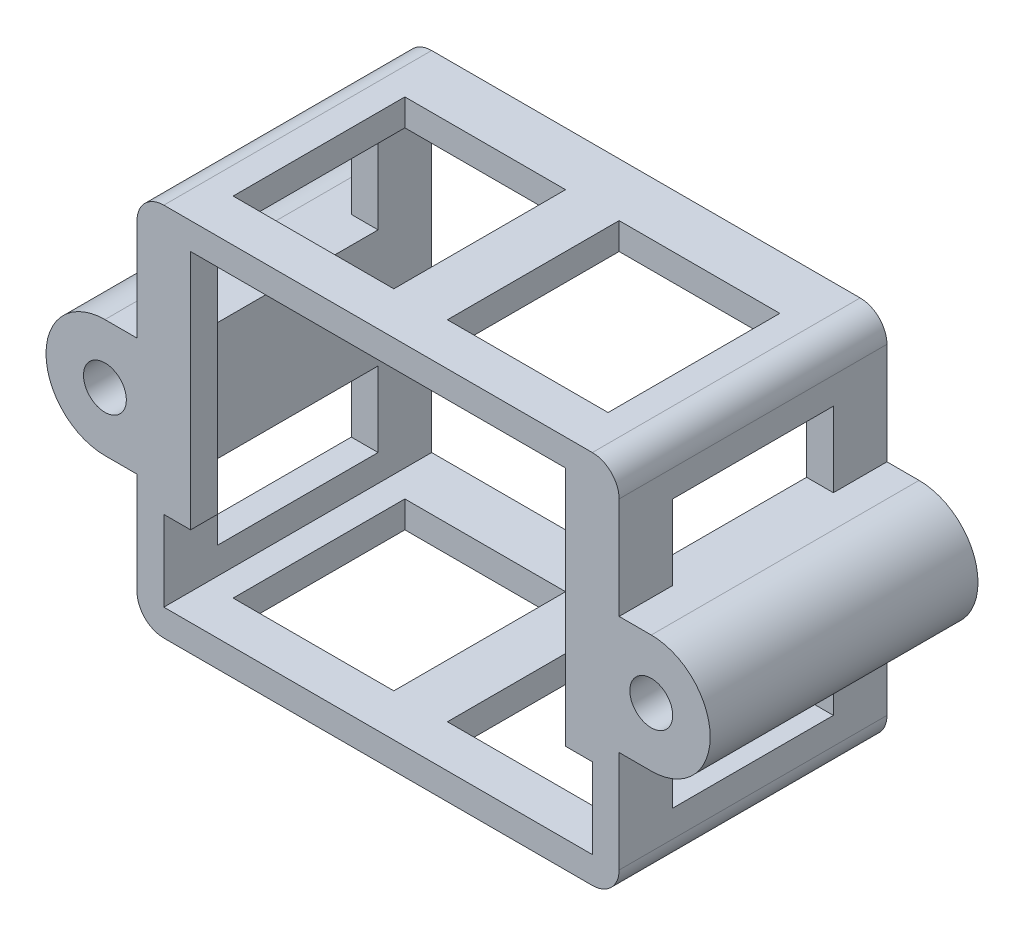
SolidWorks part; units mm, degrees
ref_plane "Спереди" through (0, 0, 0) normal (0, 0, 1) x (1, 0, 0)
ref_plane "Сверху" through (0, 0, 0) normal (0, 1, 0) x (1, 0, 0)
ref_plane "Справа" through (0, 0, 0) normal (1, 0, 0) x (0, 0, -1)
sketch "Эскиз2" plane through (0, 0, 0) normal (0, 0, 1) x (1, 0, 0)
  line L1 (-76.3548, 38.3226) -> (-58.3548, 38.3226)
  line L2 (-76.3548, 38.3226) -> (-76.3548, 24.3226)
  line L3 (-76.3548, 24.3226) -> (-58.3548, 24.3226)
  line L4 (-58.3548, 38.3226) -> (-58.3548, 24.3226)
  dimension "D1" = 18
  dimension "D2" = 14
extrude "Бобышка-Вытянуть1" add sketch "Эскиз2" along normal blind 4
shell "Оболочка1" thickness 1
sketch "Эскиз3" plane through (0, 0, 1) normal (0, 0, 1) x (1, 0, 0)
  line L0 (-70.8548, 35.3226) -> (-68.3548, 35.3226)
  line L1 (-75.3548, 37.3226) -> (-72.8548, 37.3226)
  line L2 (-75.3548, 37.3226) -> (-75.3548, 35.3226)
  line L3 (-75.3548, 35.3226) -> (-72.8548, 35.3226)
  line L4 (-72.8548, 37.3226) -> (-72.8548, 35.3226)
  line L5 (-70.8548, 37.3226) -> (-70.8548, 35.3226)
  line L6 (-70.8548, 37.3226) -> (-68.3548, 37.3226)
  line L7 (-68.3548, 37.3226) -> (-68.3548, 35.3226)
  line L8 (-66.3548, 35.3226) -> (-63.8548, 35.3226)
  line L9 (-66.3548, 37.3226) -> (-66.3548, 35.3226)
  line L10 (-66.3548, 37.3226) -> (-63.8548, 37.3226)
  line L11 (-63.8548, 37.3226) -> (-63.8548, 35.3226)
  line L12 (-61.8548, 35.3226) -> (-59.3548, 35.3226)
  line L13 (-61.8548, 37.3226) -> (-61.8548, 35.3226)
  line L14 (-61.8548, 37.3226) -> (-59.3548, 37.3226)
  line L15 (-59.3548, 37.3226) -> (-59.3548, 35.3226)
  line L16 (-70.8548, 31.9926) -> (-68.3548, 31.9926)
  line L17 (-70.8548, 33.9926) -> (-70.8548, 31.9926)
  line L18 (-70.8548, 33.9926) -> (-68.3548, 33.9926)
  line L19 (-68.3548, 33.9926) -> (-68.3548, 31.9926)
  line L20 (-66.3548, 31.9926) -> (-63.8548, 31.9926)
  line L21 (-66.3548, 33.9926) -> (-66.3548, 31.9926)
  line L22 (-66.3548, 33.9926) -> (-63.8548, 33.9926)
  line L23 (-63.8548, 33.9926) -> (-63.8548, 31.9926)
  line L24 (-61.8548, 31.9926) -> (-59.3548, 31.9926)
  line L25 (-61.8548, 33.9926) -> (-61.8548, 31.9926)
  line L26 (-61.8548, 33.9926) -> (-59.3548, 33.9926)
  line L27 (-59.3548, 33.9926) -> (-59.3548, 31.9926)
  line L28 (-70.8548, 28.6626) -> (-68.3548, 28.6626)
  line L29 (-70.8548, 30.6626) -> (-70.8548, 28.6626)
  line L30 (-70.8548, 30.6626) -> (-68.3548, 30.6626)
  line L31 (-68.3548, 30.6626) -> (-68.3548, 28.6626)
  line L32 (-66.3548, 28.6626) -> (-63.8548, 28.6626)
  line L33 (-66.3548, 30.6626) -> (-66.3548, 28.6626)
  line L34 (-66.3548, 30.6626) -> (-63.8548, 30.6626)
  line L35 (-63.8548, 30.6626) -> (-63.8548, 28.6626)
  line L36 (-61.8548, 28.6626) -> (-59.3548, 28.6626)
  line L37 (-61.8548, 30.6626) -> (-61.8548, 28.6626)
  line L38 (-61.8548, 30.6626) -> (-59.3548, 30.6626)
  line L39 (-59.3548, 30.6626) -> (-59.3548, 28.6626)
  line L40 (-70.8548, 25.3326) -> (-68.3548, 25.3326)
  line L41 (-70.8548, 27.3326) -> (-70.8548, 25.3326)
  line L42 (-70.8548, 27.3326) -> (-68.3548, 27.3326)
  line L43 (-68.3548, 27.3326) -> (-68.3548, 25.3326)
  line L44 (-66.3548, 25.3326) -> (-63.8548, 25.3326)
  line L45 (-66.3548, 27.3326) -> (-66.3548, 25.3326)
  line L46 (-66.3548, 27.3326) -> (-63.8548, 27.3326)
  line L47 (-63.8548, 27.3326) -> (-63.8548, 25.3326)
  line L48 (-61.8548, 25.3326) -> (-59.3548, 25.3326)
  line L49 (-61.8548, 27.3326) -> (-61.8548, 25.3326)
  line L50 (-61.8548, 27.3326) -> (-59.3548, 27.3326)
  line L51 (-59.3548, 27.3326) -> (-59.3548, 25.3326)
  line L52 (-75.3548, 31.9926) -> (-72.8548, 31.9926)
  line L53 (-75.3548, 33.9926) -> (-75.3548, 31.9926)
  line L54 (-75.3548, 33.9926) -> (-72.8548, 33.9926)
  line L55 (-72.8548, 33.9926) -> (-72.8548, 31.9926)
  line L56 (-75.3548, 28.6626) -> (-72.8548, 28.6626)
  line L57 (-75.3548, 30.6626) -> (-75.3548, 28.6626)
  line L58 (-75.3548, 30.6626) -> (-72.8548, 30.6626)
  line L59 (-72.8548, 30.6626) -> (-72.8548, 28.6626)
  line L60 (-75.3548, 25.3326) -> (-72.8548, 25.3326)
  line L61 (-75.3548, 27.3326) -> (-75.3548, 25.3326)
  line L62 (-75.3548, 27.3326) -> (-72.8548, 27.3326)
  line L63 (-72.8548, 27.3326) -> (-72.8548, 25.3326)
  dimension "D1" = 2
  dimension "D2" = 2.5
  dimension "D3" = 4
  dimension "D4" = 4
extrude "Вырез-Вытянуть1" cut sketch "Эскиз3" against normal blind 4
sketch "Эскиз4" plane through (-76.3548, 0, 0) normal (-1, 0, 0) x (0, 0, 1)
  line L0 (4, 38.3226) -> (4, 24.3226) construction
  line L1 (4, 34.3226) -> (2.5, 34.3226)
  line L2 (4, 34.3226) -> (4, 28.3226)
  line L3 (4, 28.3226) -> (2.5, 28.3226)
  line L4 (2.5, 34.3226) -> (2.5, 28.3226)
  line L8 (4, 24.3226) -> (0, 24.3226) construction
  dimension "D1" = 1.5
  dimension "D2" = 6
  dimension "D3" = 4
extrude "Бобышка-Вытянуть2" add sketch "Эскиз4" along normal blind 5
sketch "Эскиз5" plane through (-58.3548, 0, 0) normal (1, 0, 0) x (0, 0, -1)
  line L0 (-4, 24.3226) -> (-4, 38.3226) construction
  line L1 (-4, 34.3226) -> (-2.5, 34.3226)
  line L2 (-4, 34.3226) -> (-4, 28.3226)
  line L3 (-4, 28.3226) -> (-2.5, 28.3226)
  line L4 (-2.5, 34.3226) -> (-2.5, 28.3226)
  line L5 (-4, 24.3226) -> (0, 24.3226) construction
  dimension "D1" = 1.5
  dimension "D2" = 6
  dimension "D3" = 4
extrude "Бобышка-Вытянуть3" add sketch "Эскиз5" along normal blind 5
sketch "Эскиз6" plane through (0, 0, 2.5) normal (0, 0, -1) x (-1, 0, 0)
  line L0 (53.3548, 28.3226) -> (53.3548, 34.3226) construction
  line L1 (53.3548, 28.3226) -> (58.3548, 28.3226) construction
  line L2 (81.3548, 34.3226) -> (81.3548, 28.3226) construction
  line L3 (81.3548, 28.3226) -> (76.3548, 28.3226) construction
  circle A0 centre (55.8548, 31.3226) radius 1.1
  circle A1 centre (78.8548, 31.3226) radius 1.1
  dimension "D1" = 2.5
  dimension "D3" = 2.5
  dimension "D2" = 3
  dimension "D4" = 3
extrude "Вырез-Вытянуть2" cut sketch "Эскиз6" against normal blind 5
fillet "Скругление1" radius 3 4 edges at (-81.3548, 28.3226, 3.25) (-81.3548, 34.3226, 3.25) (-53.3548, 28.3226, 3.25) (-53.3548, 34.3226, 3.25)
sketch "Эскиз7" plane through (0, 0, 4) normal (0, 0, 1) x (1, 0, 0)
  line L0 (-76.3548, 28.3226) -> (-76.3548, 24.3226) construction
  line L1 (-82.2728, 35.9476) -> (-76.3548, 35.9476)
  line L2 (-82.2728, 35.9476) -> (-82.2728, 27.6498)
  line L3 (-82.2728, 27.6498) -> (-76.3548, 27.6498)
  line L4 (-76.3548, 35.9476) -> (-76.3548, 27.6498)
extrude "Вырез-Вытянуть3" cut sketch "Эскиз7" against normal blind 10
sketch "Эскиз8" plane through (0, 0, 4) normal (0, 0, 1) x (1, 0, 0)
  line L1 (-75.3548, 37.3226) -> (-75.3548, 25.3226) construction
  line L2 (-77.5548, 33.5226) -> (-76.3548, 33.5226)
  line L3 (-76.3548, 38.3226) -> (-76.3548, 24.3226) construction
  line L4 (-76.3548, 33.5226) -> (-76.3548, 29.1226)
  line L5 (-76.3548, 29.1226) -> (-77.5548, 29.1226)
  arc A1 (-77.5548, 33.5226) -> (-77.5548, 29.1226) centre (-77.5548, 31.3226) ccw
  circle A2 centre (-77.5548, 31.3226) radius 0.7
  dimension "D1" = 2.2
extrude "Бобышка-Вытянуть5" add sketch "Эскиз8" against normal blind 3
sketch "Эскиз9" plane through (0, 0, 4) normal (0, 0, 1) x (1, 0, 0)
  line L0 (-58.3548, 34.3226) -> (-58.3548, 38.3226) construction
  line L1 (-58.3548, 35.1277) -> (-53.0718, 35.1277)
  line L2 (-58.3548, 35.1277) -> (-58.3548, 27.2525)
  line L3 (-58.3548, 27.2525) -> (-53.0718, 27.2525)
  line L4 (-53.0718, 35.1277) -> (-53.0718, 27.2525)
extrude "Вырез-Вытянуть6" cut sketch "Эскиз9" against normal blind 3
sketch "Эскиз10" plane through (0, 0, 4) normal (0, 0, 1) x (1, 0, 0)
  line L1 (-59.3548, 25.3226) -> (-59.3548, 37.3226) construction
  line L2 (-57.1548, 33.5226) -> (-58.3548, 33.5226)
  line L3 (-58.3548, 24.3226) -> (-58.3548, 38.3226) construction
  line L4 (-58.3548, 33.5226) -> (-58.3548, 29.1226)
  line L5 (-58.3548, 29.1226) -> (-57.1548, 29.1226)
  arc A0 (-57.1548, 33.5226) -> (-57.1548, 29.1226) centre (-57.1548, 31.3226) cw
  circle A1 centre (-57.1548, 31.3226) radius 0.7
  dimension "D1" = 2.2
extrude "Бобышка-Вытянуть6" add sketch "Эскиз10" against normal blind 3
sketch "Эскиз11" plane through (0, 0, 1) normal (0, 0, -1) x (-1, 0, 0)
  line L0 (57.1548, 33.5226) -> (58.3548, 33.5226)
  line L1 (58.3548, 33.5226) -> (58.3548, 29.1226)
  line L2 (58.3548, 29.1226) -> (57.1548, 29.1226)
  line L3 (77.5548, 33.5226) -> (76.3548, 33.5226)
  line L4 (76.3548, 33.5226) -> (76.3548, 29.1226)
  line L5 (76.3548, 29.1226) -> (77.5548, 29.1226)
  arc A0 (77.5548, 33.5226) -> (77.5548, 29.1226) centre (77.5548, 31.3226) cw
  arc A1 (77.5548, 29.1226) -> (77.5548, 33.5226) centre (77.5548, 31.3226) ccw construction
  arc A2 (57.1548, 33.5226) -> (57.1548, 29.1226) centre (57.1548, 31.3226) ccw
  arc A3 (57.1548, 33.5226) -> (57.1548, 29.1226) centre (57.1548, 31.3226) ccw construction
  circle A4 centre (57.1548, 31.3226) radius 0.7
  circle A5 centre (77.5548, 31.3226) radius 0.7
extrude "Бобышка-Вытянуть7" add sketch "Эскиз11" along normal up to surface (1 mm away) up to face at (-65.1048, 29.6626, 0)
fillet "Скругление6" radius 1 6 edges at (-79.7548, 31.3226, 0) (-76.9548, 33.5226, 0) (-76.9548, 29.1226, 0) (-54.9548, 31.3226, 0) (-57.7548, 29.1226, 0) (-57.7548, 33.5226, 0)
sketch "Эскиз12" plane through (0, 0, 0) normal (0, 0, -1) x (-1, 0, 0)
  line L1 (53.0801, 41.0959) -> (83.9727, 41.0959)
  line L2 (53.0801, 41.0959) -> (53.0801, 19.1768)
  line L3 (53.0801, 19.1768) -> (83.9727, 19.1768)
  line L4 (83.9727, 41.0959) -> (83.9727, 19.1768)
extrude "Вырез-Вытянуть7" cut sketch "Эскиз12" against normal blind 1
sketch "Эскиз13" plane through (0, 0, 4) normal (0, 0, 1) x (1, 0, 0)
  line L1 (-75.3548, 37.3226) -> (-59.3548, 37.3226)
  line L2 (-75.3548, 37.3226) -> (-75.3548, 25.3226)
  line L3 (-75.3548, 25.3226) -> (-59.3548, 25.3226)
  line L4 (-59.3548, 37.3226) -> (-59.3548, 25.3226)
  line L5 (-58.3548, 24.3226) -> (-76.3548, 24.3226)
  line L6 (-58.3548, 24.3226) -> (-58.3548, 38.3226)
  line L7 (-58.3548, 38.3226) -> (-76.3548, 38.3226)
  line L8 (-76.3548, 24.3226) -> (-76.3548, 38.3226)
extrude "Бобышка-Вытянуть8" add sketch "Эскиз13" along normal blind 2
sketch "Эскиз14" plane through (0, 0, 4) normal (0, 0, 1) x (1, 0, 0)
  line L0 (-77.5548, 29.1226) -> (-76.3548, 29.1226) construction
  line L1 (-77.5548, 33.5226) -> (-76.3548, 33.5226)
  line L2 (-76.3548, 33.5226) -> (-76.3548, 29.1226)
  line L3 (-76.3548, 29.1226) -> (-77.5548, 29.1226)
  line L4 (-57.1548, 33.5226) -> (-58.3548, 33.5226)
  line L5 (-58.3548, 33.5226) -> (-58.3548, 29.1226)
  line L6 (-58.3548, 29.1226) -> (-57.1548, 29.1226)
  arc A0 (-77.5548, 33.5226) -> (-77.5548, 29.1226) centre (-77.5548, 31.3226) ccw
  arc A1 (-57.1548, 33.5226) -> (-57.1548, 29.1226) centre (-57.1548, 31.3226) cw
  arc A2 (-57.1548, 29.1226) -> (-57.1548, 33.5226) centre (-57.1548, 31.3226) ccw construction
  circle A3 centre (-57.1548, 31.3226) radius 0.7
  circle A4 centre (-77.5548, 31.3226) radius 0.7
extrude "Бобышка-Вытянуть9" add sketch "Эскиз14" along normal blind 2
sketch "Эскиз15" plane through (0, 0, 6) normal (0, 0, 1) x (1, 0, 0)
  line L1 (-58.3548, 38.3226) -> (-60.3548, 38.3226)
  line L2 (-58.3548, 38.3226) -> (-58.3548, 28.3226)
  line L3 (-58.3548, 28.3226) -> (-60.3548, 28.3226)
  line L4 (-60.3548, 38.3226) -> (-60.3548, 28.3226)
  line L5 (-76.3548, 38.3226) -> (-74.3548, 38.3226)
  line L6 (-76.3548, 38.3226) -> (-76.3548, 28.3226)
  line L7 (-76.3548, 28.3226) -> (-74.3548, 28.3226)
  line L8 (-74.3548, 38.3226) -> (-74.3548, 28.3226)
  dimension "D1" = 10
  dimension "D2" = 10
  dimension "D3" = 2
  dimension "D4" = 2
extrude "Бобышка-Вытянуть11" add sketch "Эскиз15" against normal blind 1
sketch "Эскиз16" plane through (0, 38.3226, 0) normal (0, 1, 0) x (1, 0, 0)
  line L0 (-58.3548, -6) -> (-76.3548, -6) construction
  line L1 (-75.3548, -2) -> (-72.3548, -2)
  line L2 (-75.3548, -2) -> (-75.3548, -5)
  line L3 (-75.3548, -5) -> (-72.3548, -5)
  line L4 (-72.3548, -2) -> (-72.3548, -5)
  line L5 (-76.3548, -1) -> (-58.3548, -1) construction
  line L6 (-76.3548, -6) -> (-76.3548, -1) construction
  line L7 (-71.0248, -2) -> (-71.0248, -5)
  line L8 (-71.0248, -2) -> (-68.0248, -2)
  line L9 (-68.0248, -2) -> (-68.0248, -5)
  line L10 (-71.0248, -5) -> (-68.0248, -5)
  line L11 (-66.6948, -2) -> (-66.6948, -5)
  line L12 (-66.6948, -2) -> (-63.6948, -2)
  line L13 (-63.6948, -2) -> (-63.6948, -5)
  line L14 (-66.6948, -5) -> (-63.6948, -5)
  line L15 (-62.3648, -2) -> (-62.3648, -5)
  line L16 (-62.3648, -2) -> (-59.3648, -2)
  line L17 (-59.3648, -2) -> (-59.3648, -5)
  line L18 (-62.3648, -5) -> (-59.3648, -5)
  line L19 (-58.3548, -1) -> (-58.3548, -6) construction
  dimension "D1" = 1
  dimension "D2" = 1
  dimension "D3" = 1
  dimension "D4" = 3
  dimension "D6" = 1.01
  dimension "D5" = 4
extrude "Вырез-Вытянуть9" cut sketch "Эскиз16" against normal through all
sketch "Эскиз17" plane through (0, 0, 1) normal (0, 0, -1) x (-1, 0, 0)
  circle A0 centre (57.1548, 31.3226) radius 1.2
  circle A1 centre (77.5548, 31.3226) radius 1.2
extrude "Вырез-Вытянуть10" cut sketch "Эскиз17" against normal through all
sketch "Эскиз18" plane through (0, 0, 1) normal (0, 0, -1) x (-1, 0, 0)
  line L1 (59.3548, 37.3226) -> (75.3548, 37.3226)
  line L2 (59.3548, 37.3226) -> (59.3548, 25.3226)
  line L3 (59.3548, 25.3226) -> (75.3548, 25.3226)
  line L4 (75.3548, 37.3226) -> (75.3548, 25.3226)
  line L5 (58.3548, 38.3226) -> (76.3548, 38.3226)
  line L6 (58.3548, 38.3226) -> (58.3548, 24.3226)
  line L7 (58.3548, 24.3226) -> (76.3548, 24.3226)
  line L8 (76.3548, 38.3226) -> (76.3548, 24.3226)
extrude "Бобышка-Вытянуть12" add sketch "Эскиз18" along normal blind 10
sketch "Эскиз19" plane through (0, 0, 1) normal (0, 0, -1) x (-1, 0, 0)
  circle A3 centre (57.1548, 31.3226) radius 1.2
  circle A4 centre (57.1548, 31.3226) radius 0.8
  circle A5 centre (77.5548, 31.3226) radius 1.2
  circle A6 centre (77.5548, 31.3226) radius 0.8
extrude "Бобышка-Вытянуть14" add sketch "Эскиз19" against normal up to surface (5 mm away) up to face at (-58.3548, 31.3226, 6)
sketch "Эскиз20" plane through (0, 0, 1) normal (0, 0, -1) x (-1, 0, 0)
  line L0 (77.5548, 29.1226) -> (76.3548, 29.1226) construction
  line L1 (77.5548, 33.5226) -> (76.3548, 33.5226)
  line L2 (76.3548, 33.5226) -> (76.3548, 29.1226)
  line L3 (76.3548, 29.1226) -> (77.5548, 29.1226)
  line L4 (57.1548, 33.5226) -> (58.3548, 33.5226)
  line L5 (58.3548, 33.5226) -> (58.3548, 29.1226)
  line L6 (58.3548, 29.1226) -> (57.1548, 29.1226)
  arc A0 (57.1548, 33.5226) -> (57.1548, 29.1226) centre (57.1548, 31.3226) ccw
  arc A1 (57.1548, 33.5226) -> (57.1548, 29.1226) centre (57.1548, 31.3226) ccw construction
  arc A2 (77.5548, 33.5226) -> (77.5548, 29.1226) centre (77.5548, 31.3226) cw
  circle A3 centre (57.1548, 31.3226) radius 0.8
  circle A4 centre (77.5548, 31.3226) radius 0.8
extrude "Бобышка-Вытянуть15" add sketch "Эскиз20" along normal up to surface (10 mm away) up to face at (-67.3548, 31.3226, -9)
sketch "Эскиз21" plane through (0, 24.3226, 0) normal (0, -1, 0) x (1, 0, 0)
  line L0 (-58.3548, -9) -> (-76.3548, -9) construction
  line L1 (-75.3548, 2) -> (-72.4155, 2)
  line L2 (-75.3548, 2) -> (-75.3548, -8)
  line L3 (-75.3548, -8) -> (-72.4155, -8)
  line L4 (-72.4155, 2) -> (-72.4155, -8)
  line L5 (-71.0248, 2) -> (-68.0248, 2)
  line L6 (-71.0248, 2) -> (-71.0248, -8)
  line L7 (-71.0248, -8) -> (-68.0248, -8)
  line L8 (-68.0248, 2) -> (-68.0248, -8)
  line L9 (-66.6948, 2) -> (-63.6503, 2)
  line L10 (-66.6948, 2) -> (-66.6948, -8)
  line L11 (-66.6948, -8) -> (-63.6503, -8)
  line L12 (-63.6503, 2) -> (-63.6503, -8)
  line L13 (-62.3648, 2) -> (-59.3648, 2)
  line L14 (-62.3648, 2) -> (-62.3648, -8)
  line L15 (-62.3648, -8) -> (-59.3648, -8)
  line L16 (-59.3648, 2) -> (-59.3648, -8)
  dimension "D1" = 1
  dimension "D2" = 1
  dimension "D3" = 1
  dimension "D4" = 1
extrude "Вырез-Вытянуть11" cut sketch "Эскиз21" against normal through all
sketch "Эскиз22" plane through (-76.3548, 0, 0) normal (-1, 0, 0) x (0, 0, 1)
  line L0 (-9, 29.1226) -> (6, 29.1226) construction
  line L1 (-8, 25.3226) -> (5, 25.3226)
  line L2 (-8, 25.3226) -> (-8, 29.1226)
  line L3 (-8, 29.1226) -> (5, 29.1226)
  line L4 (5, 25.3226) -> (5, 29.1226)
  line L5 (6, 24.3226) -> (-9, 24.3226) construction
  line L6 (-9, 24.3226) -> (-9, 29.1226) construction
  line L7 (6, 29.1226) -> (6, 24.3226) construction
  line L8 (-9, 33.5226) -> (6, 33.5226) construction
  line L9 (-8, 37.3226) -> (5, 37.3226)
  line L10 (-8, 37.3226) -> (-8, 33.5226)
  line L11 (-8, 33.5226) -> (5, 33.5226)
  line L12 (5, 37.3226) -> (5, 33.5226)
  line L13 (6, 38.3226) -> (-9, 38.3226) construction
  dimension "D1" = 1
  dimension "D2" = 1
  dimension "D3" = 1
  dimension "D4" = 1
extrude "Вырез-Вытянуть12" cut sketch "Эскиз22" against normal through all
sketch "Эскиз23" plane through (0, 0, -9) normal (0, 0, -1) x (-1, 0, 0)
  line L1 (53.5049, 39.479) -> (81.3941, 39.479)
  line L2 (53.5049, 39.479) -> (53.5049, 22.5003)
  line L3 (53.5049, 22.5003) -> (81.3941, 22.5003)
  line L4 (81.3941, 39.479) -> (81.3941, 22.5003)
extrude "Вырез-Вытянуть13" cut sketch "Эскиз23" against normal blind 5
sketch "Эскиз24" plane through (0, 0, -4) normal (0, 0, -1) x (-1, 0, 0)
  line L1 (59.3648, 37.3226) -> (75.3548, 37.3226)
  line L2 (59.3648, 37.3226) -> (59.3648, 25.3226)
  line L3 (59.3648, 25.3226) -> (75.3548, 25.3226)
  line L4 (75.3548, 37.3226) -> (75.3548, 25.3226)
  line L5 (76.3548, 24.3226) -> (58.3548, 24.3226)
  line L6 (76.3548, 24.3226) -> (76.3548, 38.3226)
  line L7 (76.3548, 38.3226) -> (58.3548, 38.3226)
  line L8 (58.3548, 24.3226) -> (58.3548, 38.3226)
extrude "Бобышка-Вытянуть16" add sketch "Эскиз24" against normal blind 2
sketch "Эскиз25" plane through (0, 0, 6) normal (0, 0, 1) x (1, 0, 0)
  line L1 (-59.3548, 25.3226) -> (-75.3548, 25.3226)
  line L2 (-59.3548, 25.3226) -> (-59.3548, 37.3398)
  line L3 (-59.3548, 37.3398) -> (-75.3548, 37.3398)
  line L4 (-75.3548, 25.3226) -> (-75.3548, 37.3398)
  line L5 (-76.3548, 38.3226) -> (-58.3548, 38.3226)
  line L6 (-76.3548, 38.3226) -> (-76.3548, 24.3226)
  line L7 (-76.3548, 24.3226) -> (-58.3548, 24.3226)
  line L8 (-58.3548, 38.3226) -> (-58.3548, 24.3226)
extrude "Бобышка-Вытянуть17" add sketch "Эскиз25" against normal blind 2
sketch "Эскиз26" plane through (-76.3548, 0, 0) normal (-1, 0, 0) x (0, 0, 1)
  line L0 (4, 37.3226) -> (4, 33.5226) construction
  line L1 (-2, 37.3226) -> (4, 37.3226)
  line L2 (-2, 37.3226) -> (-2, 36.3226)
  line L3 (-2, 36.3226) -> (4, 36.3226)
  line L4 (4, 37.3226) -> (4, 36.3226)
  line L5 (4, 29.1226) -> (4, 25.3226) construction
  line L6 (-2, 25.3226) -> (4, 25.3226)
  line L7 (-2, 25.3226) -> (-2, 26.3226)
  line L8 (-2, 26.3226) -> (4, 26.3226)
  line L9 (4, 25.3226) -> (4, 26.3226)
  line L10 (6, 24.3226) -> (-4, 24.3226) construction
  line L11 (6, 38.3226) -> (-4, 38.3226) construction
  dimension "D1" = 2
  dimension "D2" = 2
extrude "Бобышка-Вытянуть18" add sketch "Эскиз26" against normal up to surface (1 mm away)
sketch "Эскиз27" plane through (-58.3548, 0, 0) normal (1, 0, 0) x (0, 0, -1)
  line L0 (2, 37.3226) -> (2, 33.5226) construction
  line L1 (-4, 37.3226) -> (2, 37.3226)
  line L2 (-4, 37.3226) -> (-4, 36.3226)
  line L3 (-4, 36.3226) -> (2, 36.3226)
  line L4 (2, 37.3226) -> (2, 36.3226)
  line L5 (2, 36.3226) -> (-4, 36.3226) construction
  line L6 (-6, 24.3226) -> (4, 24.3226) construction
  line L7 (2, 25.3226) -> (-4, 25.3226)
  line L8 (2, 25.3226) -> (2, 26.3226)
  line L9 (2, 26.3226) -> (-4, 26.3226)
  line L10 (-4, 25.3226) -> (-4, 26.3226)
  line L11 (-6, 38.3226) -> (4, 38.3226) construction
  dimension "D1" = 2
  dimension "D2" = 2
extrude "Бобышка-Вытянуть19" add sketch "Эскиз27" against normal up to surface (1.01 mm away) up to face at (-59.3648, 31.3226, -3)
sketch "Эскиз28" plane through (0, 38.3226, 0) normal (0, 1, 0) x (1, 0, 0)
  line L1 (-75.3548, 2) -> (-59.3648, 2)
  line L2 (-75.3548, 2) -> (-75.3548, -4)
  line L3 (-75.3548, -4) -> (-59.3648, -4)
  line L4 (-59.3648, 2) -> (-59.3648, -4)
extrude "Бобышка-Вытянуть20" add sketch "Эскиз28" against normal up to surface (1 mm away) up to face at (-69.5248, 37.3226, 1.5)
sketch "Эскиз29" plane through (0, 24.3226, 0) normal (0, -1, 0) x (1, 0, 0)
  line L1 (-75.3548, 4) -> (-59.3648, 4)
  line L2 (-75.3548, 4) -> (-75.3548, -2)
  line L3 (-75.3548, -2) -> (-59.3648, -2)
  line L4 (-59.3648, 4) -> (-59.3648, -2)
extrude "Бобышка-Вытянуть21" add sketch "Эскиз29" against normal up to surface (1 mm away)
sketch "Эскиз30" plane through (0, 24.3226, 0) normal (0, -1, 0) x (1, 0, 0)
  line L0 (-76.3548, 6) -> (-76.3548, -4) construction
  line L1 (-74.3548, 4.4125) -> (-68.3548, 4.4125)
  line L2 (-74.3548, 4.4125) -> (-74.3548, -2)
  line L3 (-74.3548, -2) -> (-68.3548, -2)
  line L4 (-68.3548, 4.4125) -> (-68.3548, -2)
  line L5 (-58.3548, -4) -> (-76.3548, -4) construction
  line L6 (-58.3548, 6) -> (-58.3548, -4) construction
  line L7 (-66.3548, 4.4125) -> (-60.3548, 4.4125)
  line L8 (-66.3548, 4.4125) -> (-66.3548, -2)
  line L9 (-66.3548, -2) -> (-60.3548, -2)
  line L10 (-60.3548, 4.4125) -> (-60.3548, -2)
  dimension "D1" = 2
  dimension "D2" = 6
  dimension "D3" = 2
  dimension "D4" = 2
  dimension "D5" = 2
  dimension "D6" = 6
extrude "Вырез-Вытянуть14" cut sketch "Эскиз30" against normal through all
fillet "Скругление7" radius 1 4 edges at (-76.3548, 24.3226, 1) (-76.3548, 38.3226, 1) (-58.3548, 24.3226, 1) (-58.3548, 38.3226, 1)
